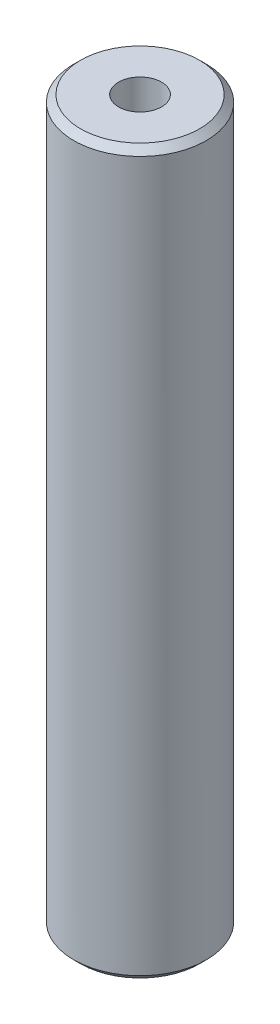
SolidWorks part; units mm, degrees
ref_plane "Front Plane" through (0, 0, 0) normal (0, 0, 1) x (1, 0, 0)
ref_plane "Top Plane" through (0, 0, 0) normal (0, 1, 0) x (1, 0, 0)
ref_plane "Right Plane" through (0, 0, 0) normal (1, 0, 0) x (0, 0, -1)
sketch "Sketch1" plane through (0, 0, 0) normal (0, 1, 0) x (1, 0, 0)
  circle A0 centre (0, 0) radius 55
  dimension "SHAFT_OD" = 110
extrude "Boss-Extrude1" add sketch "Sketch1" along normal blind 600
sketch "Sketch2" plane through (0, 0, 0) normal (0, 1, 0) x (1, 0, 0)
  circle A0 centre (0, 0) radius 17.8303
  dimension "BORE_D" = 35.6605
extrude "Cut-Extrude1" cut sketch "Sketch2" along normal through all
chamfer "Chamfer1" distance 5.6418 angle 45 2 edges at (0, 600, 55) (0, 0, 55)
